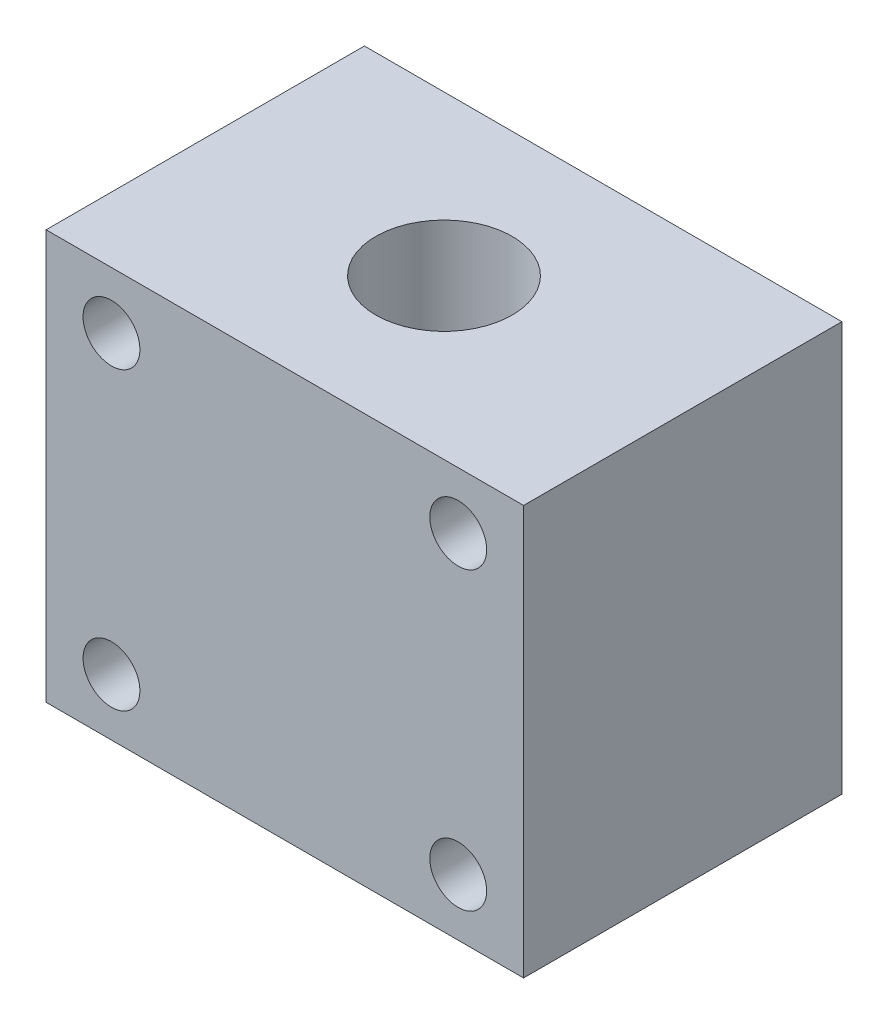
SolidWorks part; units mm, degrees
ref_plane "前视基准面" through (0, 0, 0) normal (0, 0, 1) x (1, 0, 0)
ref_plane "上视基准面" through (0, 0, 0) normal (0, 1, 0) x (1, 0, 0)
ref_plane "右视基准面" through (0, 0, 0) normal (1, 0, 0) x (0, 0, -1)
sketch "草图1" plane through (0, 0, 0) normal (0, 1, 0) x (1, 0, 0)
  line L1 (-21, -14) -> (21, -14)
  line L2 (-21, -14) -> (-21, 14)
  line L3 (-21, 14) -> (21, 14)
  line L4 (21, -14) -> (21, 14)
  line L5 (-21, -14) -> (21, 14) construction
  line L6 (-21, 14) -> (21, -14) construction
  circle A0 centre (0, 0) radius 6
  point P0 (0, 0)
  dimension "D3" = 12
  dimension "D1" = 28
  dimension "D2" = 42
extrude "凸台-拉伸2" add sketch "草图1" along normal blind 18
extrude "凸台-拉伸3" add sketch "草图1<2>" against normal blind 18
sketch "草图1<2>" plane through (0, 0, 0) normal (0, 1, 0) x (1, 0, 0) same geometry as "草图1"
sketch "草图3" plane through (0, 0, 0) normal (0, 0, 1) x (1, 0, 0)
  line L0 (0, -15.4) -> (0, 15.4) construction
  line L1 (-15.25, -13) -> (15.25, -13) construction
  line L2 (-15.25, -13) -> (-15.25, 13) construction
  line L3 (-15.25, 13) -> (15.25, 13) construction
  line L4 (15.25, -13) -> (15.25, 13) construction
  line L5 (-15.25, -13) -> (15.25, 13) construction
  line L6 (-15.25, 13) -> (15.25, -13) construction
  line L7 (15.4, 0) -> (-15.4, 0) construction
  circle A0 centre (15.25, 13) radius 2.5
  circle A1 centre (-15.25, 13) radius 2.5
  circle A2 centre (15.25, -13) radius 2.5
  circle A3 centre (-15.25, -13) radius 2.5
  point P0 (0, 0)
  dimension "D3" = 5
  dimension "D1" = 30.5
  dimension "D2" = 26
extrude "切除-拉伸3" cut sketch "草图3" along direction (0, 0, -1) on the side against the normal through all both and the other way through all
